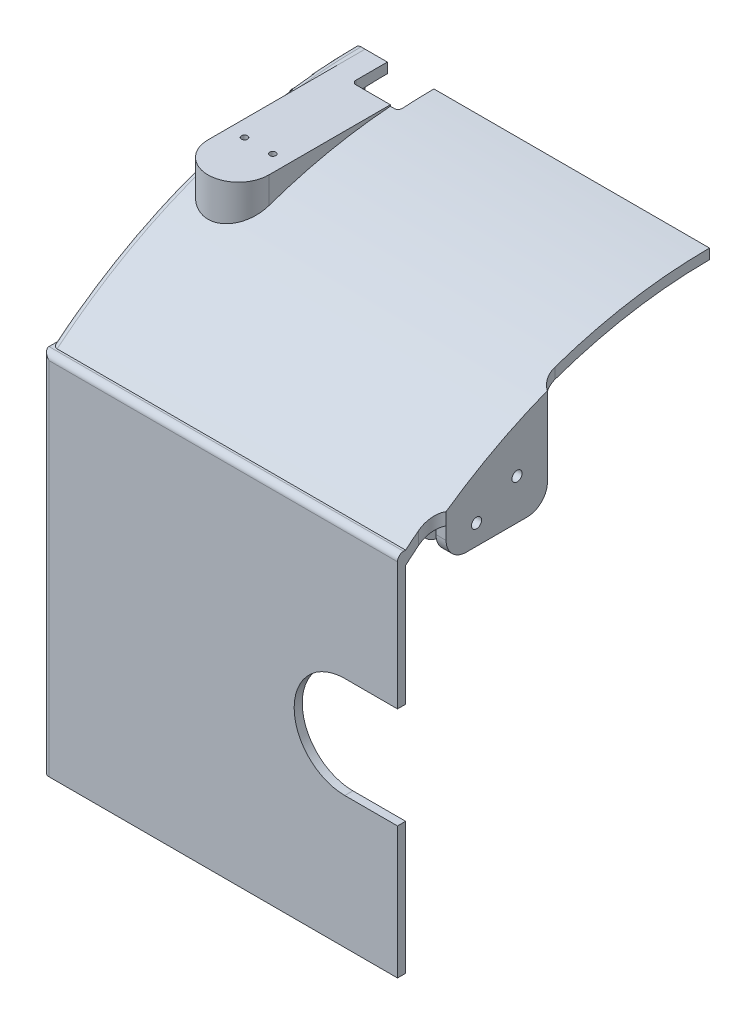
SolidWorks part; units mm, degrees
ref_plane "前视基准面" through (0, 0, 0) normal (0, 0, 1) x (1, 0, 0)
ref_plane "上视基准面" through (0, 0, 0) normal (0, 1, 0) x (1, 0, 0)
ref_plane "右视基准面" through (0, 0, 0) normal (1, 0, 0) x (0, 0, -1)
sketch "草图1" plane through (0, 0, 0) normal (1, 0, 0) x (0, 0, -1)
  circle A0 centre (0, 0) radius 235
  dimension "D1" = 470
extrude "凸台-拉伸1" add sketch "草图1" along normal blind 5
sketch "草图2" plane through (5, 0, 0) normal (1, 0, 0) x (0, 0, -1)
  circle A0 centre (0, 0) radius 230
  circle A1 centre (0, 0) radius 235
  circle A2 centre (0, 0) radius 235
  dimension "D1" = 0
  dimension "D2" = 5
extrude "凸台-拉伸2" add sketch "草图2" along normal blind 170
sketch "草图3" plane through (0, 0, 0) normal (-1, 0, 0) x (0, 0, 1)
  line L1 (150, 185) -> (240, 185)
  line L2 (150, 185) -> (150, -15)
  line L3 (150, -15) -> (240, -15)
  line L4 (240, 185) -> (240, -15)
  dimension "D1" = 200
  dimension "D2" = 90
  dimension "D3" = 150
  dimension "D4" = 15
extrude "切除-拉伸1" cut sketch "草图3" against normal through all
sketch "草图4" plane through (0, 0, 0) normal (-1, 0, 0) x (0, 0, 1)
  line L0 (0, 0) -> (268.19, 0)
  line L1 (268.19, 0) -> (268.19, -263.4037)
  line L2 (268.19, -263.4037) -> (-260.445, -263.4037)
  line L3 (-260.445, -263.4037) -> (-260.445, 244.2139)
  line L4 (-260.445, 244.2139) -> (0, 244.2139)
  line L5 (0, 244.2139) -> (0, 0)
extrude "切除-拉伸2" cut sketch "草图4" against normal through all
sketch "草图5" plane through (175, 0, 0) normal (1, 0, 0) x (0, 0, -1)
  line L0 (-135, 192.3538) -> (-135, 170)
  line L1 (-135, 170) -> (-85, 170)
  line L2 (-85, 170) -> (-85, 219.089)
  arc A0 (0, 235) -> (-150, 180.9005) centre (0, 0) ccw construction
  arc A1 (-85, 219.089) -> (-135, 192.3538) centre (0, 0) ccw
  dimension "D1" = 170
  dimension "D2" = 85
  dimension "D3" = 135
extrude "凸台-拉伸3" add sketch "草图5" along normal blind 5
ref_plane "基准面1" through (167, 0, 0) normal (1, 0, 0) x (0, 0, -1)
sketch "草图6" plane through (167, 0, 0) normal (1, 0, 0) x (0, 0, -1)
  line L3 (-135, 192.3538) -> (-135, 170)
  line L4 (-135, 170) -> (-85, 170)
  line L5 (-85, 170) -> (-85, 219.089)
  line L6 (-135, 192.3538) -> (-135, 170)
  line L7 (-135, 170) -> (-85, 170)
  line L8 (-85, 170) -> (-85, 219.089)
  arc A1 (-85, 219.089) -> (-135, 192.3538) centre (0, 0) ccw
  arc A2 (-85, 219.089) -> (-135, 192.3538) centre (0, 0) ccw
  dimension "D1" = 0
extrude "凸台-拉伸4" add sketch "草图6" against normal blind 5
ref_plane "基准面2" through (59, 0, 0) normal (1, 0, 0) x (0, 0, -1)
sketch "草图7" plane through (59, 0, 0) normal (1, 0, 0) x (0, 0, -1)
  line L3 (-85, 170) -> (-85, 213.7171)
  line L4 (-135, 186.2122) -> (-135, 170)
  line L5 (-135, 170) -> (-85, 170)
  line L6 (-85, 170) -> (-85, 213.7171)
  line L7 (-135, 186.2122) -> (-135, 170)
  line L8 (-135, 170) -> (-85, 170)
  arc A1 (-85, 213.7171) -> (-135, 186.2122) centre (0, 0) ccw
  arc A2 (-85, 213.7171) -> (-135, 186.2122) centre (0, 0) ccw
  dimension "D1" = 0
extrude "凸台-拉伸5" add sketch "草图7" against normal blind 5
sketch "草图8" plane through (180, 0, 0) normal (1, 0, 0) x (0, 0, -1)
  line L0 (-85, 170) -> (-85, 219.089) construction
  circle A0 centre (-120, 180) radius 2.5
  circle A1 centre (-100, 190) radius 2.5
  dimension "D1" = 5
  dimension "D5" = 15
  dimension "D2" = 190
  dimension "D3" = 20
  dimension "D4" = 180
extrude "切除-拉伸3" cut sketch "草图8" against normal blind 25
fillet "圆角1" radius 10 6 edges at (56.5, 170, 135) (56.5, 170, 85) (164.5, 170, 85) (164.5, 170, 135) (177.5, 170, 135) (177.5, 170, 85)
fillet "圆角2" radius 10 2 edges at (175, 189.283, 135) (175, 216.4031, 85)
sketch "草图10" plane through (0, 0, 150) normal (0, 0, 1) x (1, 0, 0)
  line L0 (0, 180.9005) -> (175, 180.9005) construction
  line L1 (0, 0) -> (175, 0)
  line L2 (0, 0) -> (0, 180.9005)
  line L3 (0, 180.9005) -> (175, 180.9005)
  line L4 (175, 0) -> (175, 180.9005)
  dimension "D1" = 175
extrude "凸台-拉伸6" add sketch "草图10" along normal blind 4
fillet "圆角3" radius 3 3 edges at (87.5, 180.9005, 154) (0, 221.0618, 79.7288) (0, 90.4503, 154)
sketch "草图11" plane through (0, 0, 0) normal (-1, 0, 0) x (0, 0, 1)
  line L0 (0, 0) -> (0, 232) construction
  line L1 (-21, 162) -> (21, 162) construction
  line L2 (-21, 162) -> (-21, 120) construction
  line L3 (-21, 120) -> (21, 120) construction
  line L4 (21, 162) -> (21, 120) construction
  circle A0 centre (21, 162) radius 1.5
  circle A1 centre (21, 120) radius 1.5
  dimension "D5" = 3
  dimension "D6" = 3
  dimension "D1" = 42
  dimension "D2" = 42
  dimension "D3" = 21
  dimension "D4" = 120
extrude "切除-拉伸5" cut sketch "草图11" against normal blind 11
ref_plane "基准面3" through (0, 235, 0) normal (0, 1, 0) x (1, 0, 0)
sketch "草图12" plane through (0, 235, 0) normal (0, 1, 0) x (1, 0, 0)
  line L0 (20, -77.5) -> (20, 0) construction
  line L1 (5, -77.5) -> (5, 0)
  line L2 (35, -77.5) -> (35, 0)
  line L3 (175, 0) -> (3, 0) construction
  line L5 (175, -76.3397) -> (175, 0) construction
  line L6 (5, 0) -> (35, 0)
  arc A0 (5, -77.5) -> (35, -77.5) centre (20, -77.5) ccw
  point P2 (85, 0)
  dimension "D2" = 77.5
  dimension "D1" = 15
  dimension "D3" = 155
  dimension "D4" = 30
extrude "凸台-拉伸7" add sketch "草图12" against normal up to surface up to face at (133.0278, 208.5453, 93.5737)
sketch "草图13" plane through (0, 235, 0) normal (0, 1, 0) x (1, 0, 0)
  line L0 (35, 0) -> (5, 0) construction
  circle A0 centre (13, -67.5) radius 1.5
  circle A1 centre (27, -67.5) radius 1.5
  point P7 (20, 0)
  dimension "D1" = 3
  dimension "D2" = 3
  dimension "D3" = 67.5
  dimension "D4" = 14
  dimension "D5" = 7
extrude "切除-拉伸6" cut sketch "草图13" against normal through all
sketch "草图14" plane through (0, 235, 0) normal (0, 1, 0) x (1, 0, 0)
  line L0 (175, 0) -> (35, 0) construction
  line L1 (16, 17.5) -> (39, 17.5)
  line L2 (16, 17.5) -> (16, -17.5)
  line L3 (16, -17.5) -> (39, -17.5)
  line L4 (39, 17.5) -> (39, -17.5)
  circle A0 centre (13, -67.5) radius 1.5 construction
  dimension "D1" = 23
  dimension "D2" = 35
  dimension "D3" = 17.5
  dimension "D4" = 3
extrude "切除-拉伸7" cut sketch "草图14" against normal through all
fillet "圆角4" radius 2 2 edges at (16, 232.1666, 17.5) (39, 231.8404, 17.5)
sketch "草图15" plane through (0, 0, 154) normal (0, 0, 1) x (1, 0, 0)
  line L0 (0, 0) -> (0, 180.9005) construction
  line L1 (3, 0) -> (175, 0) construction
  line L2 (149, 115) -> (175, 115)
  line L3 (175, 0) -> (175, 177.9005) construction
  line L4 (175, 115) -> (175, 65)
  line L5 (175, 65) -> (149, 65)
  arc A0 (149, 115) -> (149, 65) centre (149, 90) ccw
  dimension "D1" = 149
  dimension "D3" = 50
  dimension "D2" = 90
extrude "切除-拉伸8" cut sketch "草图15" against normal blind 10
sketch "草图16" plane through (0, 0, 0) normal (-1, 0, 0) x (0, 0, 1)
  line L1 (151, 0) -> (0, 0) construction
  line L2 (0, 0) -> (0, 232) construction
  circle A0 centre (97.5, 0) radius 15
  dimension "D1" = 30
  dimension "D2" = 97.5
  dimension "D3" = 0
extrude "切除-拉伸9" cut sketch "草图16" against normal blind 10
sketch "草图17" plane through (0, 0, 0) normal (-1, 0, 0) x (0, 0, 1)
  line L0 (82.5, 0) -> (0, 0) construction
  line L1 (-38.4205, 21) -> (21, 21) construction
  line L2 (-38.4205, 21) -> (-38.4205, -34.8153) construction
  line L3 (-38.4205, -34.8153) -> (21, -34.8153) construction
  line L4 (21, 21) -> (21, -34.8153) construction
  line L5 (0, 0) -> (0, 232) construction
  circle A0 centre (21, 21) radius 1.5
  dimension "D3" = 3
  dimension "D1" = 21
  dimension "D2" = 21
extrude "切除-拉伸10" cut sketch "草图17" against normal blind 10
chamfer "倒角1" distance 0.5 angle 45 1 edges at (0, 21, 22.5)
